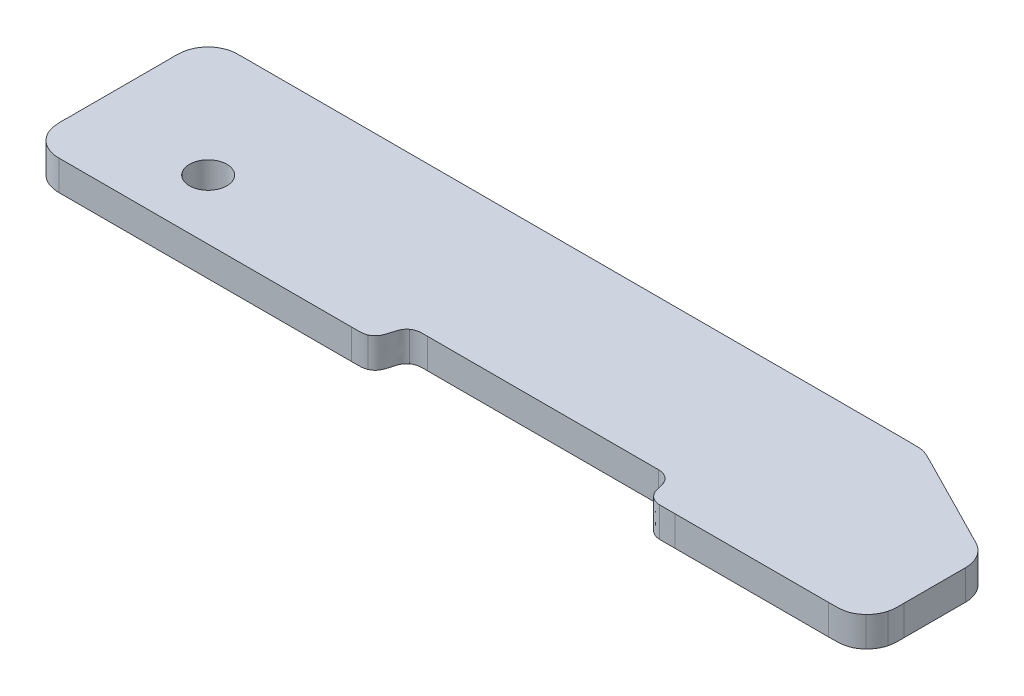
SolidWorks part; units mm, degrees
ref_plane "Front Plane" through (0, 0, 0) normal (0, 0, 1) x (1, 0, 0)
ref_plane "Top Plane" through (0, 0, 0) normal (0, 1, 0) x (1, 0, 0)
ref_plane "Right Plane" through (0, 0, 0) normal (1, 0, 0) x (0, 0, -1)
sketch "Imported Profile" plane through (0, 0, 0) normal (0, 1, 0) x (1, 0, 0)
  spline S0 degree 3 poles (178.0582, 21.1546) (178.0578, 16.8138) (178.0575, 12.466) (178.0571, 8.1183) knots 0 0 0 0 1 1 1 1
  spline S1 degree 3 poles (178.0571, 8.1183) (178.0575, 7.0503) (178.1268, 5.9962) (177.8377, 4.935) knots 0 0 0 0 1 1 1 1
  spline S2 degree 3 poles (177.8377, 4.935) (177.5208, 3.7568) (176.9764, 2.8473) (176.1014, 1.9998) knots 0 0 0 0 1 1 1 1
  spline S3 degree 3 poles (176.1014, 1.9998) (174.117, 0.105) (172.3462, 0.2359) (169.9209, 0.2359) knots 0 0 0 0 1 1 1 1
  spline S4 degree 3 poles (169.9209, 0.2359) (161.2323, 0.2359) (152.5369, 0.2359) (143.8484, 0.2359) knots 0 0 0 0 1 1 1 1
  spline S5 degree 3 poles (143.8484, 0.2359) (141.6642, 0.2359) (139.4869, 0.2359) (137.3096, 0.2359) knots 0 0 0 0 1 1 1 1
  spline S6 degree 3 poles (137.3096, 0.2359) (136.2209, 0.2359) (135.1392, 0.2014) (134.0505, 0.2359) knots 0 0 0 0 1 1 1 1
  spline S7 degree 3 poles (134.0505, 0.2359) (132.8999, 0.2704) (131.8595, 0.918) (131.3289, 1.9377) knots 0 0 0 0 1 1 1 1
  spline S8 degree 3 poles (131.3289, 1.9377) (130.819, 2.9161) (130.8811, 4.0324) (130.316, 5.0039) knots 0 0 0 0 1 1 1 1
  spline S9 degree 3 poles (130.316, 5.0039) (129.7373, 6.003) (128.6831, 6.5817) (127.5324, 6.5817) knots 0 0 0 0 1 1 1 1
  spline S10 degree 3 poles (127.5324, 6.5817) (125.3551, 6.5817) (123.1778, 6.5817) (121.0005, 6.5817) knots 0 0 0 0 1 1 1 1
  spline S11 degree 3 poles (121.0005, 6.5817) (112.2844, 6.5817) (103.5752, 6.5817) (94.8591, 6.5817) knots 0 0 0 0 1 1 1 1
  spline S12 degree 3 poles (94.8591, 6.5817) (90.5045, 6.5817) (86.143, 6.5817) (81.7815, 6.5817) knots 0 0 0 0 1 1 1 1
  spline S13 degree 3 poles (81.7815, 6.5817) (80.6929, 6.5817) (79.6042, 6.5817) (78.5156, 6.5817) knots 0 0 0 0 1 1 1 1
  spline S14 degree 3 poles (78.5156, 6.5817) (77.3994, 6.5817) (76.3727, 6.7195) (75.3461, 5.9685) knots 0 0 0 0 1 1 1 1
  spline S15 degree 3 poles (75.3461, 5.9685) (73.3755, 4.5285) (74.5055, 1.6759) (71.963, 0.5184) knots 0 0 0 0 1 1 1 1
  spline S16 degree 3 poles (71.963, 0.5184) (71.1224, 0.1325) (69.5721, 0.2359) (68.7315, 0.2359) knots 0 0 0 0 1 1 1 1
  spline S17 degree 3 poles (68.7315, 0.2359) (67.6429, 0.2359) (66.5542, 0.2359) (65.4656, 0.2359) knots 0 0 0 0 1 1 1 1
  spline S18 degree 3 poles (65.4656, 0.2359) (63.2883, 0.2359) (61.1041, 0.2359) (58.9268, 0.2359) knots 0 0 0 0 1 1 1 1
  spline S19 degree 3 poles (58.9268, 0.2359) (54.5653, 0.2359) (50.2107, 0.2359) (45.8492, 0.2359) knots 0 0 0 0 1 1 1 1
  spline S20 degree 3 poles (45.8492, 0.2359) (37.1538, 0.2359) (28.4515, 0.2359) (19.7492, 0.2359) knots 0 0 0 0 1 1 1 1
  spline S21 degree 3 poles (19.7492, 0.2359) (15.4014, 0.2359) (11.0468, 0.2359) (6.6991, 0.2359) knots 0 0 0 0 1 1 1 1
  spline S22 degree 3 poles (6.6991, 0.2359) (4.3634, 0.2359) (2.2618, 1.3865) (1.0905, 3.4329) knots 0 0 0 0 1 1 1 1
  spline S23 degree 3 poles (1.0905, 3.4329) (-0.0326, 5.4035) (0.2568, 7.8082) (0.2568, 9.8201) knots 0 0 0 0 1 1 1 1
  spline S24 degree 3 poles (0.2568, 9.8201) (0.2568, 14.1678) (0.2568, 18.5156) (0.2568, 22.8564) knots 0 0 0 0 1 1 1 1
  spline S25 degree 3 poles (0.2568, 22.8564) (0.2568, 25.0337) (0.2568, 27.2041) (0.2568, 29.3745) knots 0 0 0 0 1 1 1 1
  spline S26 degree 3 poles (0.2568, 29.3745) (0.2568, 31.6) (-0.0119, 33.6464) (1.4833, 35.6859) knots 0 0 0 0 1 1 1 1
  spline S27 degree 3 poles (1.4833, 35.6859) (2.2136, 36.685) (3.0611, 37.3464) (4.198, 37.815) knots 0 0 0 0 1 1 1 1
  spline S28 degree 3 poles (4.198, 37.815) (5.2453, 38.2422) (6.2788, 38.2835) (7.3675, 38.2835) knots 0 0 0 0 1 1 1 1
  spline S29 degree 3 poles (7.3675, 38.2835) (9.5379, 38.2835) (11.7083, 38.2835) (13.8856, 38.2835) knots 0 0 0 0 1 1 1 1
  spline S30 degree 3 poles (13.8856, 38.2835) (18.2264, 38.2835) (22.5741, 38.2835) (26.9218, 38.2835) knots 0 0 0 0 1 1 1 1
  spline S31 degree 3 poles (26.9218, 38.2835) (44.4092, 38.2835) (61.8964, 38.2835) (79.3906, 38.2835) knots 0 0 0 0 1 1 1 1
  spline S32 degree 3 poles (79.3906, 38.2835) (96.8573, 38.2835) (114.3308, 38.2835) (131.7975, 38.2835) knots 0 0 0 0 1 1 1 1
  spline S33 degree 3 poles (131.7975, 38.2835) (136.1589, 38.2835) (140.5273, 38.2835) (144.8888, 38.2835) knots 0 0 0 0 1 1 1 1
  spline S34 degree 3 poles (144.8888, 38.2835) (145.4745, 38.2835) (150.8419, 38.304) (151.4345, 38.2216) knots 0 0 0 0 1 1 1 1
  spline S35 degree 3 poles (151.4345, 38.2216) (152.5645, 38.063) (153.5015, 37.5601) (154.48, 37.0571) knots 0 0 0 0 1 1 1 1
  spline S36 degree 3 poles (154.48, 37.0571) (155.4515, 36.5679) (156.423, 36.0718) (157.3945, 35.5757) knots 0 0 0 0 1 1 1 1
  spline S37 degree 3 poles (157.3945, 35.5757) (161.2875, 33.5914) (165.1735, 31.6139) (169.0665, 29.6295) knots 0 0 0 0 1 1 1 1
  spline S38 degree 3 poles (169.0665, 29.6295) (170.038, 29.1334) (171.0095, 28.6373) (171.981, 28.1412) knots 0 0 0 0 1 1 1 1
  spline S39 degree 3 poles (171.981, 28.1412) (172.9526, 27.652) (173.9379, 27.1973) (174.8818, 26.6529) knots 0 0 0 0 1 1 1 1
  spline S40 degree 3 poles (174.8818, 26.6529) (176.8455, 25.523) (178.0582, 23.4214) (178.0582, 21.1546) knots 0 0 0 0 1 1 1 1
  spline S41 degree 3 poles (29.6228, 12.9345) (29.6228, 10.7434) (27.8451, 8.9657) (25.6541, 8.9657) knots 0 0 0 0 1 1 1 1
  spline S42 degree 3 poles (25.6541, 8.9657) (23.463, 8.9657) (21.6853, 10.7434) (21.6853, 12.9345) knots 0 0 0 0 1 1 1 1
  spline S43 degree 3 poles (21.6853, 12.9345) (21.6853, 15.1256) (23.463, 16.9032) (25.6541, 16.9032) knots 0 0 0 0 1 1 1 1
  spline S44 degree 3 poles (25.6541, 16.9032) (27.8451, 16.9032) (29.6228, 15.1256) (29.6228, 12.9345) knots 0 0 0 0 1 1 1 1
sketch "Sketch4" plane through (0, 0, 0) normal (0, 1, 0) x (1, 0, 0)
  circle A0 centre (25.6541, 12.9345) radius 3.9688
  spline S0 degree 3 poles (-1370.1409, 1323.9207) (1038.8939, -923.7451) (-712.4339, 988.9517) (1696.6083, -1258.7214) knots -41.774564 -41.774564 -41.774564 -41.774564 42.774639 42.774639 42.774639 42.774639 only from (157.3945, 35.5757) to (169.0665, 29.6295) construction
  spline S1 degree 3 poles (376.0605, 1875.4206) (-1479.5997, -1082.3544) (1829.0874, 1138.1816) (-51.3256, -1816.4188) knots -369.840284 -369.840284 -369.840284 -369.840284 371.612933 371.612933 371.612933 371.612933 only from (169.0665, 29.6295) to (171.981, 28.1412) construction
  spline S2 degree 3 poles (908.269, 1887.0169) (-659.8258, -1783.9957) (1006.9937, 1838.9417) (-567.5164, -1829.9023) knots -24.219115 -24.219115 -24.219115 -24.219115 24.76741 24.76741 24.76741 24.76741 only from (171.981, 28.1412) to (174.8818, 26.6529) construction
  spline S3 degree 3 poles (634.5941, -1913.7013) (-663.7986, 1873.0389) (1345.8725, -1636.8189) (-1263.0141, 1399.4192) knots -12.393463 -12.393463 -12.393463 -12.393463 13.40497 13.40497 13.40497 13.40497 only from (174.8818, 26.6529) to (178.0582, 21.1546) construction
  spline S4 degree 3 poles (177.8889, -1978.7637) (178.3368, 3312.0916) (177.7768, -3302.3891) (178.2264, 2008.1061) knots -74.483894 -74.483894 -74.483894 -74.483894 76.608418 76.608418 76.608418 76.608418 only from (178.0582, 21.1546) to (178.0571, 8.1183) construction
  spline S5 degree 3 poles (2171.4545, 166.8586) (-1816.6914, -74.7286) (2173.4037, 84.1055) (-1817.1039, -134.2335) knots -16.54842 -16.54842 -16.54842 -16.54842 16.876064 16.876064 16.876064 16.876064 only from (178.0571, 8.1183) to (177.8377, 4.935) construction
  spline S6 degree 3 poles (709.4157, 1930.8999) (-539.7061, -1730.6163) (1128.2343, 1617.8505) (-1058.8853, -1567.9445) knots -19.565605 -19.565605 -19.565605 -19.565605 20.7495 20.7495 20.7495 20.7495 only from (177.8377, 4.935) to (176.1014, 1.9998) construction
  spline S7 degree 3 poles (833.5382, 1890.7975) (-498.1038, -1848.355) (931.456, 1807.4864) (-764.8748, -1766.3119) knots -8.63166 -8.63166 -8.63166 -8.63166 10.296247 10.296247 10.296247 10.296247 only from (176.1014, 1.9998) to (169.9209, 0.2359) construction
  spline S8 degree 3 poles (-1830.031, 0.2359) (4381.8556, 0.2359) (-4068.1572, 0.2359) (2143.7916, 0.2359) knots -63.871392 -63.871392 -63.871392 -63.871392 64.873514 64.873514 64.873514 64.873514 only from (169.9209, 0.2359) to (143.8484, 0.2359) construction
  spline S9 degree 3 poles (2143.7844, 0.2359) (-1331.6123, 0.2359) (1604.7294, 0.2359) (-1862.6509, 0.2359) knots -60.473146 -60.473146 -60.473146 -60.473146 62.39629 62.39629 62.39629 62.39629 only from (143.8484, 0.2359) to (137.3096, 0.2359) construction
  spline S10 degree 3 poles (490.5198, -1967.6601) (-98.9506, 1969.9859) (368.1575, -1970.1717) (-208.4723, 1970.0419) knots -26.362878 -26.362878 -26.362878 -26.362878 27.038245 27.038245 27.038245 27.038245 only from (137.3096, 0.2359) to (134.0505, 0.2359) construction
  spline S11 degree 3 poles (-1291.7134, 1397.3141) (1777.1165, -1170.1098) (-1670.4385, 908.9937) (2031.8713, -608.5517) knots -15.752288 -15.752288 -15.752288 -15.752288 16.705304 16.705304 16.705304 16.705304 only from (134.0505, 0.2359) to (131.3289, 1.9377) construction
  spline S12 degree 3 poles (2085.5986, 426.3777) (-1812.936, -467.9319) (2074.8556, 473.9409) (-1824.4844, -417.1797) knots -11.275893 -11.275893 -11.275893 -11.275893 12.231094 12.231094 12.231094 12.231094 only from (131.3289, 1.9377) to (130.316, 5.0039) construction
  spline S13 degree 3 poles (-1843.081, 303.1764) (2044.6357, -616.4683) (-1660.8929, 930.7797) (1720.8277, -1194.9113) knots -16.246574 -16.246574 -16.246574 -16.246574 17.589455 17.589455 17.589455 17.589455 only from (130.316, 5.0039) to (127.5324, 6.5817) construction
  spline S14 degree 3 poles (-1872.393, 6.5817) (6146.2332, 6.5817) (-5897.6947, 6.5817) (2120.9175, 6.5817) knots -461.690422 -461.690422 -461.690422 -461.690422 462.690096 462.690096 462.690096 462.690096 only from (127.5324, 6.5817) to (121.0005, 6.5817) construction
  spline S15 degree 3 poles (2120.9851, 6.5817) (-481.4997, 6.5817) (697.3592, 6.5817) (-1905.1308, 6.5817) knots -40.349467 -40.349467 -40.349467 -40.349467 41.349524 41.349524 41.349524 41.349524 only from (121.0005, 6.5817) to (94.8591, 6.5817) construction
  spline S16 degree 3 poles (-1905.0989, 6.5817) (3392.2369, 6.5817) (-3235.2001, 6.5817) (2081.7359, 6.5817) knots -74.617885 -74.617885 -74.617885 -74.617885 76.742175 76.742175 76.742175 76.742175 only from (94.8591, 6.5817) to (81.7815, 6.5817) construction
  spline S17 degree 3 poles (-1918.1787, 6.5817) (3831.2809, 6.5817) (-3670.9821, 6.5817) (2078.4727, 6.5817) knots -402.015798 -402.015798 -402.015798 -402.015798 403.015652 403.015652 403.015652 403.015652 only from (81.7815, 6.5817) to (78.5156, 6.5817) construction
  spline S18 degree 3 poles (328.2274, 1990.6477) (-93.8184, -1981.2991) (226.0489, 1997.3818) (-100.5912, -1986.1981) knots -12.323971 -12.323971 -12.323971 -12.323971 12.610585 12.610585 12.610585 12.610585 only from (78.5156, 6.5817) to (75.3461, 5.9685) construction
  spline S19 degree 3 poles (1909.0335, -792.0449) (-1746.7322, 853.3885) (1894.4289, -847.3372) (-1760.6043, 801.1145) knots -6.000439 -6.000439 -6.000439 -6.000439 6.915353 6.915353 6.915353 6.915353 only from (75.3461, 5.9685) to (71.963, 0.5184) construction
  spline S20 degree 3 poles (-1741.4222, 843.5146) (1951.0212, -802.4628) (-1827.6146, 763.5106) (1932.5612, -724.841) knots -10.425283 -10.425283 -10.425283 -10.425283 11.524314 11.524314 11.524314 11.524314 only from (71.963, 0.5184) to (68.7315, 0.2359) construction
  spline S21 degree 3 poles (2068.7081, 0.2359) (-494.9121, 0.2359) (625.9794, 0.2359) (-1934.5108, 0.2359) knots -330.094334 -330.094334 -330.094334 -330.094334 331.813063 331.813063 331.813063 331.813063 only from (68.7315, 0.2359) to (65.4656, 0.2359) construction
  spline S22 degree 3 poles (-1934.4558, 0.2359) (2544.0676, 0.2359) (-2419.691, 0.2359) (2058.8868, 0.2359) knots -55.124015 -55.124015 -55.124015 -55.124015 56.124335 56.124335 56.124335 56.124335 only from (65.4656, 0.2359) to (58.9268, 0.2359) construction
  spline S23 degree 3 poles (2058.9124, 0.2359) (-1141.0787, 0.2359) (1245.8467, 0.2359) (-1954.0877, 0.2359) knots -46.140285 -46.140285 -46.140285 -46.140285 47.139812 47.139812 47.139812 47.139812 only from (58.9268, 0.2359) to (45.8492, 0.2359) construction
  spline S24 degree 3 poles (-1954.0586, 0.2359) (4959.9478, 0.2359) (-4936.8779, 0.2359) (2019.6311, 0.2359) knots -83.969481 -83.969481 -83.969481 -83.969481 86.191752 86.191752 86.191752 86.191752 only from (45.8492, 0.2359) to (19.7492, 0.2359) construction
  spline S25 degree 3 poles (-1980.2129, 0.2359) (3024.9489, 0.2359) (-2998.4869, 0.2359) (2006.6319, 0.2359) knots -58.007247 -58.007247 -58.007247 -58.007247 59.007019 59.007019 59.007019 59.007019 only from (19.7492, 0.2359) to (6.6991, 0.2359) construction
  spline S26 degree 3 poles (-1518.6587, 1280.0571) (1804.2894, -892.1883) (-1949.0224, 475.8394) (1993.1986, -27.5117) knots -13.599929 -13.599929 -13.599929 -13.599929 14.087522 14.087522 14.087522 14.087522 only from (6.6991, 0.2359) to (1.0905, 3.4329) construction
  spline S27 degree 3 poles (1850.5432, 762.9152) (-1832.6938, -877.3868) (1813.9623, 937.6913) (-1792.4897, -876.4778) knots -9.455497 -9.455497 -9.455497 -9.455497 11.007676 11.007676 11.007676 11.007676 only from (1.0905, 3.4329) to (0.2568, 9.8201) construction
  spline S28 degree 3 poles (0.2568, 2009.7703) (0.2568, -3300.6804) (0.2568, 3313.8414) (0.2568, -1977.1345) knots -75.608062 -75.608062 -75.608062 -75.608062 75.484586 75.484586 75.484586 75.484586 only from (0.2568, 9.8201) to (0.2568, 22.8564) construction
  spline S29 degree 3 poles (0.2568, -1977.0858) (0.2568, 1498.0415) (0.2568, -1437.7248) (0.2568, 2029.2923) knots -60.694704 -60.694704 -60.694704 -60.694704 62.624087 62.624087 62.624087 62.624087 only from (0.2568, 22.8564) to (0.2568, 29.3745) construction
  spline S30 degree 3 poles (-1979.6988, -248.5886) (1985.873, 192.3153) (-1989.6613, -101.2351) (1993.0338, 217.8919) knots -9.782615 -9.782615 -9.782615 -9.782615 10.068378 10.068378 10.068378 10.068378 only from (0.2568, 29.3745) to (1.4833, 35.6859) construction
  spline S31 degree 3 poles (-1232.7755, -1535.103) (1340.6323, 1343.5524) (-1511.5406, -1057.7752) (1768.3466, 974.3779) knots -19.756295 -19.756295 -19.756295 -19.756295 20.879982 20.879982 20.879982 20.879982 only from (1.4833, 35.6859) to (4.198, 37.815) construction
  spline S32 degree 3 poles (-383.1861, -1924.2448) (358.5547, 1991.6677) (-381.6585, -1905.6519) (513.4478, 1972.461) knots -16.73895 -16.73895 -16.73895 -16.73895 18.892251 18.892251 18.892251 18.892251 only from (4.198, 37.815) to (7.3675, 38.2835) construction
  spline S33 degree 3 poles (-1992.578, 38.2835) (1476.3701, 38.2835) (-1463.0889, 38.2835) (2013.8636, 38.2835) knots -61.407639 -61.407639 -61.407639 -61.407639 61.491697 61.491697 61.491697 61.491697 only from (7.3675, 38.2835) to (13.8856, 38.2835) construction
  spline S34 degree 3 poles (2013.8663, 38.2835) (-3282.4938, 38.2835) (3342.9854, 38.2835) (-1973.0515, 38.2835) knots -74.794721 -74.794721 -74.794721 -74.794721 76.92726 76.92726 76.92726 76.92726 only from (13.8856, 38.2835) to (26.9218, 38.2835) construction
  spline S35 degree 3 poles (-1973.0671, 38.2835) (-282.1228, 38.2835) (366.949, 38.2835) (2079.3673, 38.2835) knots -33.258534 -33.258534 -33.258534 -33.258534 33.951426 33.951426 33.951426 33.951426 only from (26.9218, 38.2835) to (79.3906, 38.2835) construction
  spline S36 degree 3 poles (79.3798, 38.2835) (-4648.3375, 38.2835) (6497.4658, 38.2835) (-1868.1201, 38.2835) knots -60.949289 -60.949289 -60.949289 -60.949289 76.032141 76.032141 76.032141 76.032141 only from (79.3906, 38.2835) to (131.7975, 38.2835) construction
  spline S37 degree 3 poles (2131.7334, 38.2835) (-2877.58, 38.2835) (3154.3213, 38.2835) (-1855.0887, 38.2835) knots -58.064419 -58.064419 -58.064419 -58.064419 59.06678 59.06678 59.06678 59.06678 only from (131.7975, 38.2835) to (144.8888, 38.2835) construction
  spline S38 degree 3 poles (2144.6774, 60.5049) (-1919.6384, 13.355) (2215.9334, 66.1673) (-1848.2672, 7.1957) knots -5.485793 -5.485793 -5.485793 -5.485793 6.486432 6.486432 6.486432 6.486432 only from (144.8888, 38.2835) to (151.4345, 38.2216) construction
  spline S39 degree 3 poles (-992.6085, -1602.0212) (1251.1464, 1698.4933) (-958.1323, -1612.5578) (1348.0175, 1641.3866) knots -15.910235 -15.910235 -15.910235 -15.910235 17.791712 17.791712 17.791712 17.791712 only from (151.4345, 38.2216) to (154.48, 37.0571) construction
  spline S40 degree 3 poles (-53.3601, -1948.7709) (107.4351, 2153.4705) (207.1509, -2082.6357) (368.8715, 2020.8147) knots -66.150823 -66.150823 -66.150823 -66.150823 68.16056 68.16056 68.16056 68.16056 only from (154.48, 37.0571) to (157.3945, 35.5757) construction
  spline S41 degree 3 poles (157.3945, 35.5757) (161.2875, 33.5914) (165.1735, 31.6139) (169.0665, 29.6295) knots 0 0 0 0 1 1 1 1
  spline S42 degree 3 poles (169.0665, 29.6295) (170.038, 29.1334) (171.0095, 28.6373) (171.981, 28.1412) knots 0 0 0 0 1 1 1 1
  spline S43 degree 3 poles (171.981, 28.1412) (172.9526, 27.652) (173.9379, 27.1973) (174.8818, 26.6529) knots 0 0 0 0 1 1 1 1
  spline S44 degree 3 poles (174.8818, 26.6529) (176.8457, 25.5229) (178.0584, 23.4211) (178.0582, 21.154) knots 0 0 0 0 1.000079 1.000079 1.000079 1.000079
  spline S45 degree 3 poles (178.0582, 21.154) (178.0578, 16.8134) (178.0575, 12.4659) (178.0571, 8.1183) knots 0.000041 0.000041 0.000041 0.000041 1 1 1 1
  spline S46 degree 3 poles (178.0571, 8.1183) (178.0575, 7.0503) (178.1268, 5.9962) (177.8377, 4.935) knots 0 0 0 0 1 1 1 1
  spline S47 degree 3 poles (177.8377, 4.935) (177.5208, 3.7568) (176.9764, 2.8473) (176.1014, 1.9998) knots 0 0 0 0 1 1 1 1
  spline S48 degree 3 poles (176.1014, 1.9998) (174.117, 0.105) (172.3462, 0.2359) (169.9209, 0.2359) knots 0 0 0 0 1 1 1 1
  spline S49 degree 3 poles (169.9209, 0.2359) (161.2323, 0.2359) (152.5369, 0.2359) (143.8484, 0.2359) knots 0 0 0 0 1 1 1 1
  spline S50 degree 3 poles (143.8484, 0.2359) (141.6642, 0.2359) (139.4869, 0.2359) (137.3096, 0.2359) knots 0 0 0 0 1 1 1 1
  spline S51 degree 3 poles (137.3096, 0.2359) (136.2209, 0.2359) (135.1392, 0.2014) (134.0505, 0.2359) knots 0 0 0 0 1 1 1 1
  spline S52 degree 3 poles (134.0505, 0.2359) (132.8999, 0.2704) (131.8595, 0.918) (131.3289, 1.9377) knots 0 0 0 0 1 1 1 1
  spline S53 degree 3 poles (131.3289, 1.9377) (130.819, 2.9161) (130.8811, 4.0324) (130.316, 5.0039) knots 0 0 0 0 1 1 1 1
  spline S54 degree 3 poles (130.316, 5.0039) (129.7373, 6.003) (128.6831, 6.5817) (127.5324, 6.5817) knots 0 0 0 0 1 1 1 1
  spline S55 degree 3 poles (127.5324, 6.5817) (125.3551, 6.5817) (123.1778, 6.5817) (121.0005, 6.5817) knots 0 0 0 0 1 1 1 1
  spline S56 degree 3 poles (121.0005, 6.5817) (112.2844, 6.5817) (103.5752, 6.5817) (94.8591, 6.5817) knots 0 0 0 0 1 1 1 1
  spline S57 degree 3 poles (94.8591, 6.5817) (90.5045, 6.5817) (86.143, 6.5817) (81.7815, 6.5817) knots 0 0 0 0 1 1 1 1
  spline S58 degree 3 poles (81.7815, 6.5817) (80.6929, 6.5817) (79.6042, 6.5817) (78.5156, 6.5817) knots 0 0 0 0 1 1 1 1
  spline S59 degree 3 poles (78.5156, 6.5817) (77.3994, 6.5817) (76.3727, 6.7195) (75.3461, 5.9685) knots 0 0 0 0 1 1 1 1
  spline S60 degree 3 poles (75.3461, 5.9685) (73.3755, 4.5285) (74.5055, 1.6759) (71.963, 0.5184) knots 0 0 0 0 1 1 1 1
  spline S61 degree 3 poles (71.963, 0.5184) (71.1224, 0.1325) (69.5721, 0.2359) (68.7315, 0.2359) knots 0 0 0 0 1 1 1 1
  spline S62 degree 3 poles (68.7315, 0.2359) (67.6429, 0.2359) (66.5542, 0.2359) (65.4656, 0.2359) knots 0 0 0 0 1 1 1 1
  spline S63 degree 3 poles (65.4656, 0.2359) (63.2883, 0.2359) (61.1041, 0.2359) (58.9268, 0.2359) knots 0 0 0 0 1 1 1 1
  spline S64 degree 3 poles (58.9268, 0.2359) (54.5653, 0.2359) (50.2107, 0.2359) (45.8492, 0.2359) knots 0 0 0 0 1 1 1 1
  spline S65 degree 3 poles (45.8492, 0.2359) (37.1538, 0.2359) (28.4515, 0.2359) (19.7492, 0.2359) knots 0 0 0 0 1 1 1 1
  spline S66 degree 3 poles (19.7492, 0.2359) (15.4014, 0.2359) (11.0468, 0.2359) (6.6991, 0.2359) knots 0 0 0 0 1 1 1 1
  spline S67 degree 3 poles (6.6991, 0.2359) (4.3634, 0.2359) (2.2618, 1.3865) (1.0905, 3.4329) knots 0 0 0 0 1 1 1 1
  spline S68 degree 3 poles (1.0905, 3.4329) (-0.0326, 5.4035) (0.2568, 7.8082) (0.2568, 9.8201) knots 0 0 0 0 1 1 1 1
  spline S69 degree 3 poles (0.2568, 9.8201) (0.2568, 14.1678) (0.2568, 18.5156) (0.2568, 22.8564) knots 0 0 0 0 1 1 1 1
  spline S70 degree 3 poles (0.2568, 22.8564) (0.2568, 25.0337) (0.2568, 27.2041) (0.2568, 29.3745) knots 0 0 0 0 1 1 1 1
  spline S71 degree 3 poles (0.2568, 29.3745) (0.2568, 31.6) (-0.0119, 33.6464) (1.4833, 35.6859) knots 0 0 0 0 1 1 1 1
  spline S72 degree 3 poles (1.4833, 35.6859) (2.2136, 36.685) (3.0611, 37.3464) (4.198, 37.815) knots 0 0 0 0 1 1 1 1
  spline S73 degree 3 poles (4.198, 37.815) (5.2453, 38.2422) (6.2788, 38.2835) (7.3675, 38.2835) knots 0 0 0 0 1 1 1 1
  spline S74 degree 3 poles (7.3675, 38.2835) (9.5379, 38.2835) (11.7083, 38.2835) (13.8856, 38.2835) knots 0 0 0 0 1 1 1 1
  spline S75 degree 3 poles (13.8856, 38.2835) (18.2264, 38.2835) (22.5741, 38.2835) (26.9218, 38.2835) knots 0 0 0 0 1 1 1 1
  spline S76 degree 3 poles (26.9218, 38.2835) (44.4092, 38.2835) (61.8964, 38.2835) (79.3906, 38.2835) knots 0 0 0 0 1 1 1 1
  spline S77 degree 3 poles (79.3906, 38.2835) (96.8573, 38.2835) (114.3308, 38.2835) (131.7975, 38.2835) knots 0 0 0 0 1 1 1 1
  spline S78 degree 3 poles (131.7975, 38.2835) (136.1589, 38.2835) (140.5273, 38.2835) (144.8888, 38.2835) knots 0 0 0 0 1 1 1 1
  spline S79 degree 3 poles (144.8888, 38.2835) (145.4745, 38.2835) (150.8419, 38.304) (151.4345, 38.2216) knots 0 0 0 0 1 1 1 1
  spline S80 degree 3 poles (151.4345, 38.2216) (152.5645, 38.063) (153.5015, 37.5601) (154.48, 37.0571) knots 0 0 0 0 1 1 1 1
  spline S81 degree 3 poles (154.48, 37.0571) (155.4515, 36.5679) (156.423, 36.0718) (157.3945, 35.5757) knots 0 0 0 0 1 1 1 1
  dimension "D1" = 7.9375
extrude "Boss-Extrude1" add sketch "Sketch4" along normal blind 6.35
